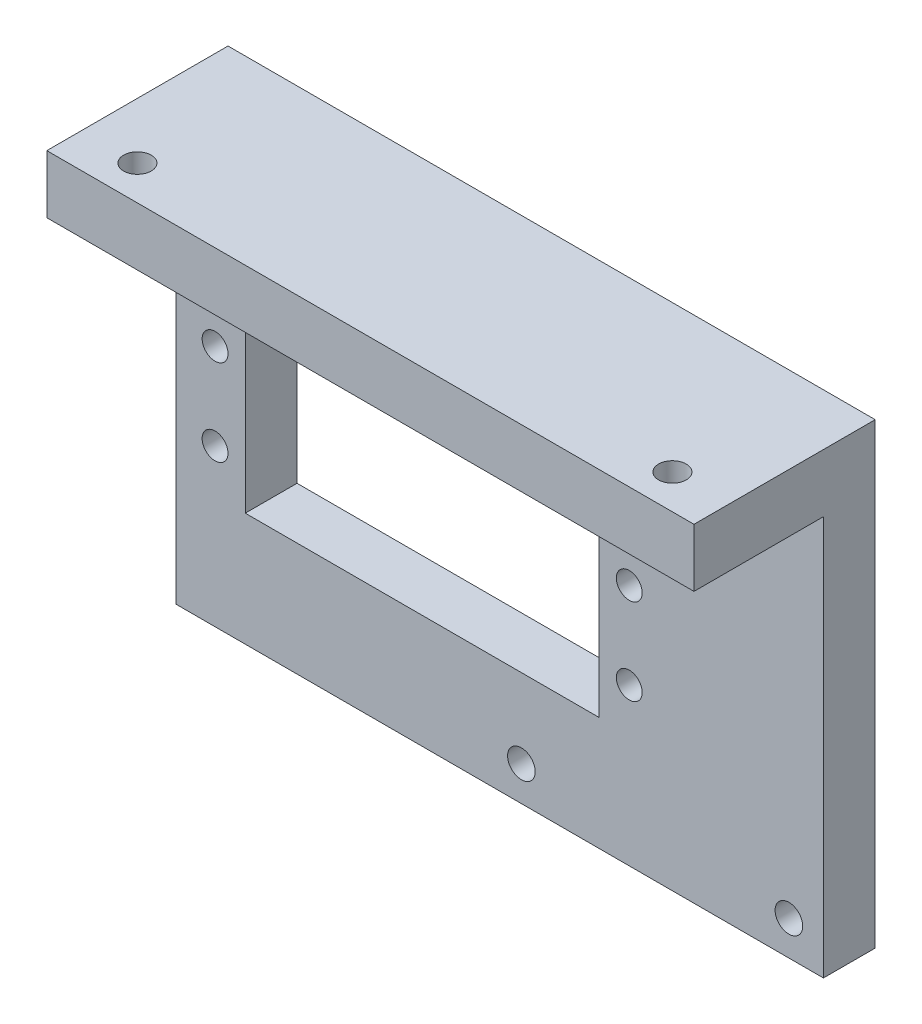
SolidWorks part; units mm, degrees
note: The reader was unsure of these and kept them because the rebuilt part matched: flange length of "Edge-Flange1".
ref_plane "Front Plane" through (0, 0, 0) normal (0, 0, 1) x (1, 0, 0)
ref_plane "Top Plane" through (0, 0, 0) normal (0, 1, 0) x (1, 0, 0)
ref_plane "Right Plane" through (0, 0, 0) normal (1, 0, 0) x (0, 0, -1)
sketch "Sketch1" plane through (0, 0, 0) normal (0, 0, 1) x (1, 0, 0)
  line L0 (-6.3777, 0) -> (6.4702, 0) construction
  line L1 (-20.5, -10) -> (20.5, -10)
  line L2 (-20.5, -10) -> (-20.5, 10)
  line L3 (-20.5, 10) -> (20.5, 10)
  line L4 (20.5, -10) -> (20.5, 10)
  line L5 (-20.5, -10) -> (20.5, 10) construction
  line L6 (-20.5, 10) -> (20.5, -10) construction
  line L8 (0, -6.4239) -> (0, 6.4239) construction
  line L9 (-28.5, -23.15) -> (46.5, -23.15)
  line L10 (-28.5, -23.15) -> (-28.5, 23.15)
  line L11 (-28.5, 23.15) -> (46.5, 23.15)
  line L12 (46.5, -23.15) -> (46.5, 23.15)
  circle A0 centre (-24, 5) radius 1.5
  circle A1 centre (24, 5) radius 1.5
  circle A2 centre (24, -5) radius 1.5
  circle A3 centre (-24, -5) radius 1.5
  point P0 (0, 0)
  point P22 (9, 23.15)
  dimension "D3" = 3
  dimension "D1" = 41
  dimension "D2" = 20
  dimension "D4" = 24
  dimension "D5" = 5
  dimension "D6" = 0
  dimension "D7" = 75
  dimension "D8" = 46.3
  dimension "D9" = 15
  dimension "D10" = 23.15
base flange "Base-Flange2" sketch "Sketch1" thickness 6 reverse thickness direction no parameters "D1"=0.7366
edge flange "Edge-Flange1" sketch "Sketch14" flange angle 90 flange length 21 flange position bend outside bend radius 0.7366 thickness 6 relief rectangular parameters "D6"=10
sketch "Sketch14" plane through (0, 23.15, 0) normal (0, 1, 0) x (-1, 0, 0)
  line L0 (-46.5, 0) -> (28.5, 0) construction
  line L1 (-46.5, 0) -> (28.5, 0)
  line L2 (-46.5, 0) -> (-46.5, 15)
  line L3 (-46.5, 15) -> (28.5, 15)
  line L4 (28.5, 15) -> (28.5, 0)
bend "EdgeBend1" bend radius 0.7366 bend angle 90 parameters "D5"=1
sketch "Sketch15" plane through (0, 29.8866, 0) normal (0, 1, 0) x (1, 0, 0)
  line L1 (-28.5, -15) -> (46.5, -15) construction
  circle A0 centre (-22, -11) radius 1.6
  circle A1 centre (40, -11) radius 1.6
  point P2 (9, -15)
  dimension "D1" = 3.2
  dimension "D3" = 4
  dimension "D4" = 31
  dimension "D5" = 3.2
  dimension "D6" = 4
  dimension "D2" = 62
extrude "Cut-Extrude1" cut sketch "Sketch15" against normal up to next normal cut yes
sketch "Sketch16" plane through (0, 0, -6) normal (0, 0, -1) x (-1, 0, 0)
  line L0 (28.5, -23.15) -> (-46.5, -23.15) construction
  line L1 (-46.5, -23.15) -> (-46.5, 23.15) construction
  circle A0 centre (-42.5, -19.15) radius 1.6
  circle A1 centre (-11.5, -19.15) radius 1.6
  dimension "D1" = 3.2
  dimension "D3" = 4
  dimension "D4" = 3.2
  dimension "D6" = 4
  dimension "D2" = 4
  dimension "D5" = 35
extrude "Cut-Extrude2" cut sketch "Sketch16" against normal up to next normal cut yes
sketch "Sketch17" plane through (0, 29.8866, 0) normal (0, 1, 0) x (1, 0, 0)
  line L1 (46.5, -15) -> (-28.5, -15)
  line L2 (46.5, -15) -> (46.5, 6)
  line L3 (46.5, 6) -> (-28.5, 6)
  line L4 (-28.5, -15) -> (-28.5, 6)
extrude "Boss-Extrude1" add sketch "Sketch17" against normal up to vertex (6.7366 mm away) up to point (-28.5, 23.15, -6)
sketch "Sketch18" plane through (0, 29.8866, 0) normal (0, 1, 0) x (1, 0, 0)
  line L0 (-28.5, -15) -> (46.5, -15) construction
  circle A0 centre (-22, -11) radius 1.6
  circle A1 centre (40, -11) radius 1.6
  point P2 (0, 0)
  dimension "D1" = 3.2
  dimension "D3" = 4
  dimension "D5" = 3.2
  dimension "D2" = 62
extrude "Cut-Extrude3" cut sketch "Sketch18" against normal up to next normal cut yes
sketch "Bend-Lines3" [suppressed] plane through (0, 0, 0) normal (0, 1, 0) x (1, 0, 0)
sketch "Bounding-Box3" [suppressed] plane through (0, 0, 0) normal (0, 1, 0) x (1, 0, 0)
sheet metal parameters "Sheet-Metal3" thickness 6 parameters "D1"=0.7366
flat pattern "Flat-Pattern3" [suppressed]
sketch "Bend-Lines4" plane through (0, 0, 0) normal (0, 1, 0) x (1, 0, 0)
sketch3d "Bounding-Box4" [suppressed]
  line L0 (28.5, -23.15, 0) -> (-46.5, -23.15, 0) construction
  line L1 (28.5, 23.15, 0) -> (-46.5, 23.15, 0) construction
  line L2 (28.5, -23.15, 0) -> (28.5, 23.15, 0) construction
  line L3 (-46.5, -23.15, 0) -> (-46.5, 23.15, 0) construction
sheet metal parameters "Sheet-Metal4" thickness 6 parameters "D1"=0.7366
flat pattern "Flat-Pattern3"
sketch "Bend-Lines4" plane through (0, 0, 0) normal (0, 0, 1) x (1, 0, 0)
  line L0 (46.5, 26.0847) -> (-28.5, 26.0847) construction
  line L1 (46.5, 26.0847) -> (-28.5, 26.0847) construction
sketch3d "Bounding-Box4" [suppressed]
  line L0 (-28.5, -23.15, 0) -> (46.5, -23.15, 0) construction
  line L1 (-28.5, 37.2828, 0) -> (46.5, 37.2828, 0) construction
  line L2 (-28.5, -23.15, 0) -> (-28.5, 37.2828, 0) construction
  line L3 (46.5, -23.15, 0) -> (46.5, 37.2828, 0) construction
bend of the flat pattern "Flatten-<EdgeBend1>1"
sheet metal parameters "Sheet-Metal5" thickness 6 parameters "D1"=0.7366
flat pattern "Flat-Pattern3"
sketch "Bend-Lines4" plane through (0, 0, 0) normal (0, 0, 1) x (1, 0, 0)
  line L0 (46.5, 26.0847) -> (-28.5, 26.0847) construction
  line L1 (46.5, 26.0847) -> (-28.5, 26.0847) construction
sketch3d "Bounding-Box4" [suppressed]
  line L0 (-28.5, -23.15, 0) -> (46.5, -23.15, 0) construction
  line L1 (-28.5, 37.2828, 0) -> (46.5, 37.2828, 0) construction
  line L2 (-28.5, -23.15, 0) -> (-28.5, 37.2828, 0) construction
  line L3 (46.5, -23.15, 0) -> (46.5, 37.2828, 0) construction
bend of the flat pattern "Flatten-<EdgeBend1>1"
sheet metal parameters "Sheet-Metal6" thickness 6 parameters "D1"=0.7366
flat pattern "Flat-Pattern3"
sketch "Bend-Lines4" plane through (0, 0, 0) normal (0, 0, 1) x (1, 0, 0)
  line L0 (46.5, 26.0847) -> (-28.5, 26.0847) construction
  line L1 (46.5, 26.0847) -> (-28.5, 26.0847) construction
sketch3d "Bounding-Box4" [suppressed]
  line L0 (-28.5, -23.15, 0) -> (46.5, -23.15, 0) construction
  line L1 (-28.5, 43.2828, 0) -> (46.5, 43.2828, 0) construction
  line L2 (-28.5, -23.15, 0) -> (-28.5, 43.2828, 0) construction
  line L3 (46.5, -23.15, 0) -> (46.5, 43.2828, 0) construction
bend of the flat pattern "Flatten-<EdgeBend1>1"
sheet metal parameters "Sheet-Metal7" thickness 6 parameters "D1"=0.7366
flat pattern "Flat-Pattern3"
sketch "Bend-Lines4" plane through (0, 0, 0) normal (0, 0, 1) x (1, 0, 0)
  point P0 (46.5, 26.0847)
  point P1 (-28.5, 26.0847)
sketch3d "Bounding-Box4" [suppressed]
  line L0 (-28.5, -23.15, 0) -> (46.5, -23.15, 0) construction
  line L1 (-28.5, 23.15, 0) -> (46.5, 23.15, 0) construction
  line L2 (-28.5, -23.15, 0) -> (-28.5, 23.15, 0) construction
  line L3 (46.5, -23.15, 0) -> (46.5, 23.15, 0) construction
bend of the flat pattern "Flatten-<EdgeBend1>1"
sheet metal parameters "Sheet-Metal8" thickness 6 parameters "D1"=0.7366
flat pattern "Flat-Pattern3"
sketch "Bend-Lines4" plane through (0, 0, 0) normal (0, 0, 1) x (1, 0, 0)
sketch3d "Bounding-Box4" [suppressed]
  line L0 (-28.5, -23.15, 0) -> (46.5, -23.15, 0) construction
  line L1 (-28.5, 23.15, 0) -> (46.5, 23.15, 0) construction
  line L2 (-28.5, -23.15, 0) -> (-28.5, 23.15, 0) construction
  line L3 (46.5, -23.15, 0) -> (46.5, 23.15, 0) construction
bend of the flat pattern "Flatten-<EdgeBend1>1"
